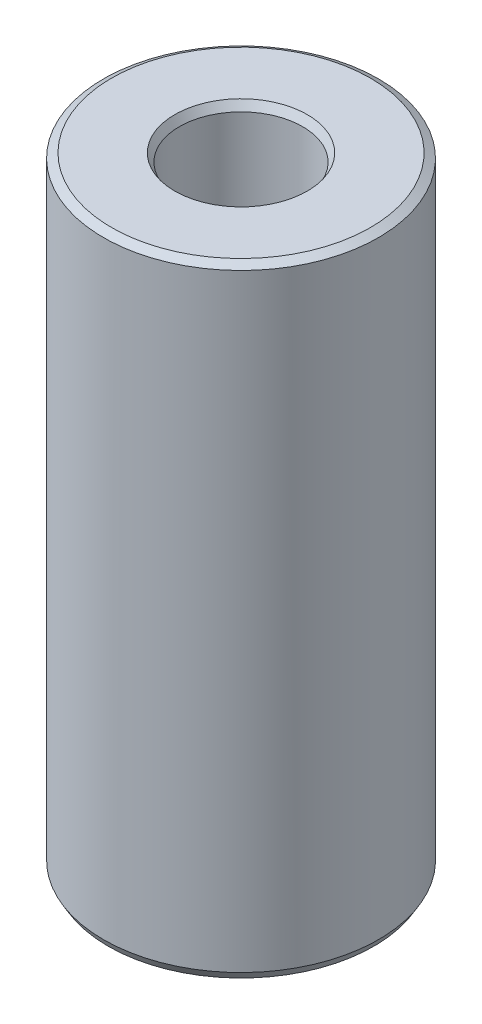
SolidWorks part; units mm, degrees
ref_plane "Front Plane" through (0, 0, 0) normal (0, 0, 1) x (1, 0, 0)
ref_plane "Top Plane" through (0, 0, 0) normal (0, 1, 0) x (1, 0, 0)
ref_plane "Right Plane" through (0, 0, 0) normal (1, 0, 0) x (0, 0, -1)
sketch "Sketch1" plane through (0, 0, 0) normal (0, 1, 0) x (1, 0, 0)
  circle A0 centre (0, 0) radius 52.5
  dimension "SLEEVE_OD" = 105
extrude "Boss-Extrude1" add sketch "Sketch1" along normal blind 236.9745
sketch "Sketch2" plane through (0, 0, 0) normal (0, 1, 0) x (1, 0, 0)
  circle A0 centre (0, 0) radius 23.5247
  dimension "BORE_D" = 47.0494
extrude "Cut-Extrude1" cut sketch "Sketch2" along normal through all
chamfer "Chamfer1" distance 1.7789 angle 60 4 edges at (0, 236.9745, 23.5247) (0, 0, 23.5247) (0, 0, 52.5) (0, 236.9745, 52.5) first distance on face at (0, 236.9745, 23.5247) first distance on face at (0, 0, 23.5247) first distance on face at (0, 236.9745, 52.5)
